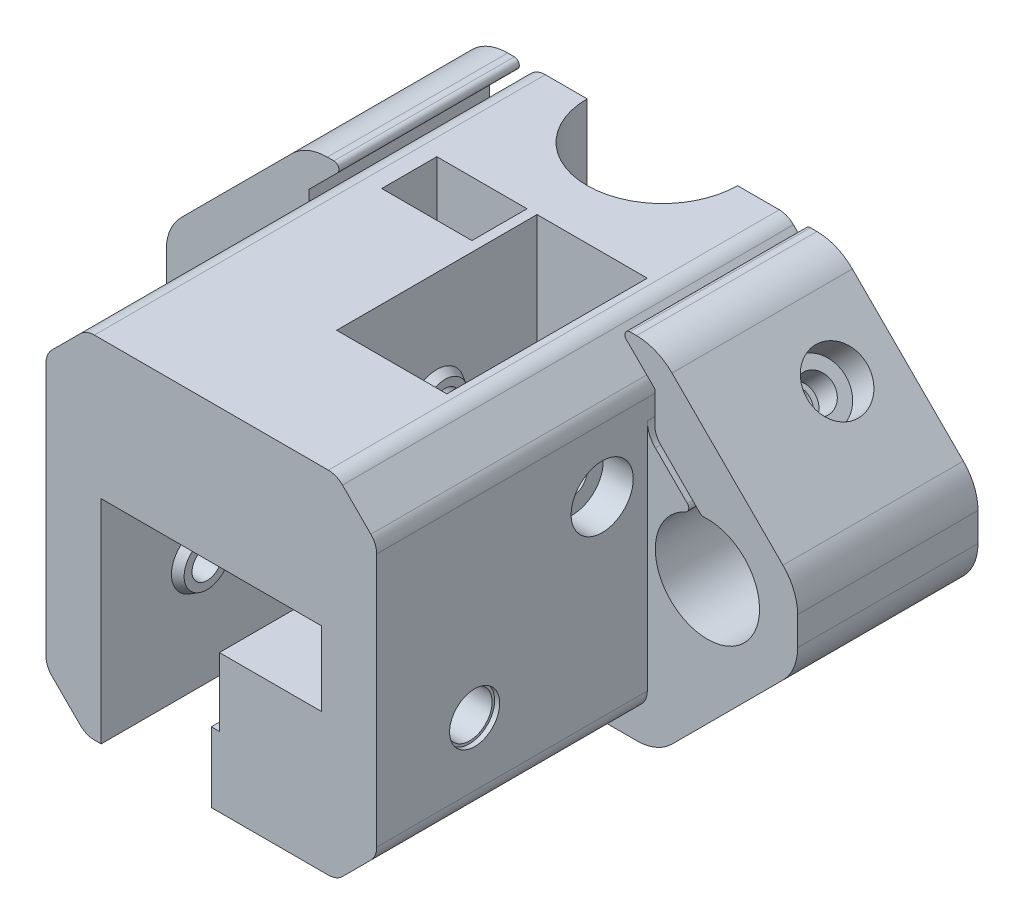
SolidWorks part; units mm, degrees
ref_plane "XY" through (0, 0, 0) normal (0, 0, 1) x (1, 0, 0)
ref_plane "XZ" through (0, 0, 0) normal (0, 1, 0) x (1, 0, 0)
ref_plane "YZ" through (0, 0, 0) normal (1, 0, 0) x (0, 0, -1)
sketch "Sketch1" plane through (0, 0, 0) normal (0, 0, 1) x (1, 0, 0)
  line L0 (-17.5, 17.5) -> (-31.5, 3.5)
  line L1 (31.5, -17.5) -> (17.5, -17.5) construction
  line L2 (31.5, -17.5) -> (31.5, -3.5) construction
  line L3 (31.5, 17.5) -> (17.5, 17.5) construction
  line L4 (-31.5, -17.5) -> (-31.5, -3.5) construction
  line L5 (31.5, -17.5) -> (-31.5, 17.5) construction
  line L6 (31.5, 17.5) -> (-31.5, -17.5) construction
  line L7 (-12.5, 17.5) -> (-16.5, 13.5)
  line L8 (-16.5, 13.5) -> (-16.5, 9.535)
  line L9 (-16.5, 9.535) -> (-21.0432, 4.9918)
  line L10 (-13.5607, 17.5) -> (-17.25, 13.8107)
  line L11 (-17.25, 13.8107) -> (-17.25, 9.8457)
  line L12 (-17.25, 9.8457) -> (-21.9273, 5.1684)
  line L13 (-17.25, 9.8457) -> (-21.5736, 5.5221) construction
  line L14 (-13.0303, 18.0303) -> (-17.25, 13.8107) construction
  line L15 (-13.5607, 17.5) -> (-17.5, 17.5)
  line L16 (0, 0) -> (-59.6161, 0) construction
  line L17 (0, 0) -> (0, 36.6742) construction
  line L18 (-17.5, -17.5) -> (-31.5, -3.5)
  line L19 (17.5, -17.5) -> (31.5, -3.5)
  line L20 (16.5, 9.535) -> (21.0432, 4.9918)
  line L21 (16.5, 13.5) -> (16.5, 9.535)
  line L22 (12.5, 17.5) -> (16.5, 13.5)
  line L23 (13.5607, 17.5) -> (17.25, 13.8107)
  line L24 (17.25, 13.8107) -> (17.25, 9.8457)
  line L25 (17.25, 9.8457) -> (21.9273, 5.1684)
  line L26 (17.5, 17.5) -> (31.5, 3.5)
  line L27 (12.5, 17.5) -> (-12.5, 17.5)
  line L28 (-17.5, 17.5) -> (-31.5, 17.5) construction
  line L29 (-31.5, 3.5) -> (-31.5, 17.5) construction
  line L30 (-31.5, -3.5) -> (-31.5, 3.5)
  line L31 (-17.5, -17.5) -> (-31.5, -17.5) construction
  line L32 (17.5, -17.5) -> (-17.5, -17.5)
  line L33 (31.5, -3.5) -> (31.5, 3.5)
  line L34 (31.5, 3.5) -> (31.5, 17.5) construction
  line L35 (17.5, 17.5) -> (13.5607, 17.5)
  arc A0 (-21.9273, 5.1684) -> (-21.0432, 4.9918) centre (-22.5, 0) ccw
  arc A1 (21.9273, 5.1684) -> (21.0432, 4.9918) centre (22.5, 0) cw
  point P0 (0, 0)
  dimension "D1" = 63
  dimension "D6" = 10.4
  dimension "D2" = 35
  dimension "D3" = 14
  dimension "D4" = 14
  dimension "D5" = 22.5
  dimension "D7" = 19
  dimension "D8" = 15
  dimension "D9" = 9.535
  dimension "D10" = 0.75
extrude "Boss-Extrude1" add sketch "Sketch1" along normal blind 18
sketch "Sketch2" plane through (0, 17.5, 0) normal (0, 1, 0) x (1, 0, 0)
  line L0 (12.5, 0) -> (-12.5, 0) construction
  line L1 (12.5, -18) -> (-12.5, -18) construction
  line L2 (-10, -18) -> (-1, -18)
  line L3 (-10, -18) -> (-10, -12.5)
  line L4 (-10, -12.5) -> (-1, -12.5)
  line L5 (-1, -18) -> (-1, -12.5)
  circle A0 centre (0, 0) radius 7.5
  point P10 (-5.5, -12.5)
  dimension "D1" = 15
  dimension "D2" = 9
  dimension "D3" = 5.5
  dimension "D4" = 5.5
extrude "Cut-Extrude1" cut sketch "Sketch2" against normal through all
fillet "Fillet1" radius 5 8 edges at (17.5, 17.5, 9) (31.5, 3.5, 9) (31.5, -3.5, 9) (17.5, -17.5, 9) (-17.5, -17.5, 9) (-31.5, -3.5, 9) (-31.5, 3.5, 9) (-17.5, 17.5, 9)
fillet "Fillet2" radius 0.5 6 edges at (-21.9273, 5.1684, 9) (-21.0432, 4.9918, 9) (21.0432, 4.9918, 9) (21.9273, 5.1684, 9) (-13.5607, 17.5, 9) (13.5607, 17.5, 9)
fillet "Fillet3" radius 2 2 edges at (17.25, 9.8457, 9) (-17.25, 9.8457, 9)
fillet "Fillet4" radius 2.75 2 edges at (-16.5, 9.535, 9) (16.5, 9.535, 9)
sketch "Sketch3" plane through (-17.5, 17.5, 0) normal (-0.7071, 0.7071, 0) x (0, 0, 1)
  line L0 (0, -2.0711) -> (0, -17.7279) construction
  circle A0 centre (6, -8.4) radius 1.75
  point P6 (-12.8431, 2.7076)
  dimension "D1" = 3.5
  dimension "D2" = 6
  dimension "D3" = 8.4
ref_plane "Plane1" through (0, 0, 6) normal (0, 0, -1) x (-1, 0, 0)
sketch "Sketch4" plane through (0, 0, 6) normal (0, 0, -1) x (-1, 0, 0)
  line L0 (23.4397, 11.5603) -> (11.3618, -0.5176) construction
  line L1 (24.6771, 10.3229) -> (22.2023, 12.7977) construction
  line L2 (23.4397, 11.5603) -> (25.561, 9.439)
  line L3 (18.9645, 16.0355) -> (30.0355, 4.9645) construction
  line L4 (25.561, 9.439) -> (23.4397, 7.3177)
  line L5 (23.4397, 7.3177) -> (22.5558, 8.2015)
  line L6 (12.8331, 0.9537) -> (23.4397, 11.5603)
  line L9 (22.5558, 8.2015) -> (14.0705, -0.2837)
  line L10 (14.0705, -0.2837) -> (12.8331, 0.9537)
  dimension "D1" = 3
  dimension "D2" = 1.75
  dimension "D3" = 3
  dimension "D4" = 15
revolve "Cut-Revolve1" cut sketch "Sketch4" angle 360 about L0
sketch "Sketch6" plane through (-6.8934, 6.8934, 0) normal (-0.7071, 0.7071, 0) x (0, 0, 1)
  line L0 (0, -2.0711) -> (0, -17.7279) construction
  line L1 (3.425, -9.8867) -> (6, -11.3734)
  line L2 (6, -11.3734) -> (8.575, -9.8867)
  line L3 (8.575, -9.8867) -> (8.575, -6.9133)
  line L4 (8.575, -6.9133) -> (6, -5.4266)
  line L5 (6, -5.4266) -> (3.425, -6.9133)
  line L6 (3.425, -6.9133) -> (3.425, -9.8867)
  circle A0 centre (6, -8.4) radius 2.575 construction
  dimension "D1" = 5.15
extrude "Cut-Extrude2" cut sketch "Sketch6" against normal blind 15
mirror "Mirror1" about plane through (0, 0, 0) normal (1, 0, 0) of "Cut-Extrude2", "Cut-Revolve1"
sketch "Sketch7" plane through (0, 0, 0) normal (0, 0, -1) x (-1, 0, 0)
  circle A0 centre (-12.5, 12.5) radius 1.6
  dimension "D1" = 3.2
  dimension "D2" = 12.5
  dimension "D3" = 12.5
extrude "Cut-Extrude3" cut sketch "Sketch7" against normal blind 10
sketch "Sketch8" plane through (0, 0, 0) normal (0, 0, -1) x (-1, 0, 0)
  circle A0 centre (-12.5, 12.5) radius 2.35
  dimension "D1" = 4.7
extrude "Cut-Extrude4" cut sketch "Sketch8" against normal blind 5
sketch "Sketch9" plane through (0, 0, 0) normal (0, 0, -1) x (-1, 0, 0)
  circle A0 centre (-12.5, 12.5) radius 2.5
  dimension "D1" = 5
extrude "Cut-Extrude5" cut sketch "Sketch9" against normal blind 0.5
mirror "Mirror2" about plane through (0, 0, 0) normal (0, 1, 0) of "Cut-Extrude5", "Cut-Extrude4", "Cut-Extrude3"
mirror "Mirror3" about plane through (0, 0, 0) normal (1, 0, 0) of "Mirror2", "Cut-Extrude5", "Cut-Extrude4", "Cut-Extrude3"
sketch "Sketch10" plane through (0, 0, 18) normal (0, 0, 1) x (1, 0, 0)
  line L0 (12.5, 17.5) -> (-1, 17.5) construction
  line L1 (16.5, 13.5) -> (12.5, 17.5) construction
  line L2 (16.5, 10.6741) -> (16.5, 13.5) construction
  line L3 (12.5, 17.5) -> (-12.5, 17.5)
  line L4 (16.5, 13.5) -> (12.5, 17.5)
  line L5 (16.5, -13.5) -> (16.5, 13.5)
  line L6 (0, -17.5) -> (0, 17.5) construction
  line L7 (0, 0) -> (16.5, 0) construction
  line L8 (-16.5, -13.5) -> (-16.5, 13.5)
  line L9 (-16.5, 13.5) -> (-12.5, 17.5)
  line L10 (-16.5, -13.5) -> (-12.5, -17.5)
  line L11 (16.5, -13.5) -> (12.5, -17.5)
  line L12 (12.5, -17.5) -> (-12.5, -17.5)
  point P14 (-16.5, 0)
extrude "Boss-Extrude2" add sketch "Sketch10" along normal offset from surface (27 mm away) 45 up to face at (-10, -12.5, 0)
sketch "Sketch11" plane through (0, 17.5, 0) normal (0, 1, 0) x (1, 0, 0)
  line L0 (-1, -12.5) -> (-10, -12.5) construction
  line L1 (0, -12.5) -> (11, -12.5)
  line L2 (0, -12.5) -> (0, -32.5)
  line L3 (0, -32.5) -> (11, -32.5)
  line L4 (11, -12.5) -> (11, -32.5)
  dimension "D1" = 20
  dimension "D2" = 11
extrude "Cut-Extrude6" cut sketch "Sketch11" against normal blind 21.2
sketch "Sketch12" plane through (0, 0, 32.5) normal (0, 0, -1) x (-1, 0, 0)
  line L0 (0, -3.7) -> (-11, -3.7) construction
  line L1 (0, -3.7) -> (-11, -3.7)
  line L2 (0, 0) -> (-16.491, 0) construction
  line L3 (-11, -3.7) -> (-11, 3.7)
  line L4 (-11, 3.7) -> (0, 3.7)
  line L5 (0, 3.7) -> (0, -3.7)
  line L6 (0, -3.7) -> (0, -3.5912)
  line M2 (-11, 17.5) -> (-11, -3.7)
  line M3 (-11, -3.7) -> (0, -3.7)
  line M4 (0, -3.7) -> (0, 17.5)
extrude "Cut-Extrude7" cut sketch "Sketch12" against normal up to surface (12.5 mm away) contours L2 L4 M4 M2 | L5 L2 L3 M3 M4 region at (5.5, -1.85, 32.5) region at (5.5, 1.85, 32.5) up to face at (0, 0, 45)
fillet "Fillet5" radius 10 1 edges at (5.5, -3.7, 12.5)
sketch "Sketch13" plane through (0, -17.5, 0) normal (0, -1, 0) x (1, 0, 0)
  line L1 (0, 45) -> (-11, 45)
  line L2 (0, 45) -> (0, 25.2)
  line L3 (0, 25.2) -> (-11, 25.2)
  line L4 (-11, 45) -> (-11, 25.2)
  dimension "D1" = 11
  dimension "D2" = 19.8
extrude "Cut-Extrude8" cut sketch "Sketch13" against normal up to surface (21.2 mm away) up to face at (5.5, 3.7, 38.75)
fillet "Fillet6" radius 10 1 edges at (-5.5, 3.7, 25.2) tangent propagation no
sketch "Sketch14" plane through (0, 0, 45) normal (0, 0, 1) x (1, 0, 0)
  line L0 (-11, 3.7) -> (11, 3.7) construction
  line L1 (11, -3.7) -> (11, 3.7) construction
  line L2 (0, -3.7) -> (11, -3.7) construction
  line L3 (0, 3.7) -> (11, 3.7)
  line L4 (11, -3.7) -> (11, 3.7)
  line L5 (0, -3.7) -> (11, -3.7)
  line L6 (0, -3.7) -> (0, 3.7)
extrude "Cut-Extrude9" cut sketch "Sketch14" against normal up to surface (12.5 mm away) up to face at (5.5, 10.4143, 32.5)
sketch "Sketch15" plane through (-11, 0, 0) normal (1, 0, 0) x (0, 0, -1)
  circle A0 centre (-35.23, -6.365) radius 2.75
  dimension "D1" = 5.5
  dimension "D2" = 35.23
  dimension "D3" = 6.365
extrude "Boss-Extrude3" add sketch "Sketch15" along normal blind 0.8 draft 30
sketch "Sketch16" plane through (0, 0, 0) normal (-1, 0, 0) x (0, 0, 1)
  line L1 (45, -3.7) -> (31, -3.7)
  line L2 (45, -3.7) -> (45, -10.515)
  line L3 (45, -10.515) -> (31, -10.515)
  line L4 (31, -3.7) -> (31, -10.515)
  dimension "D1" = 6.815
  dimension "D2" = 14
extrude "Cut-Extrude10" cut sketch "Sketch16" against normal blind 0.8
ref_plane "Plane2" through (0, 0, 35.23) normal (0, 0, 1) x (1, 0, 0)
sketch "Sketch17" plane through (0, 0, 35.23) normal (0, 0, 1) x (1, 0, 0)
  line L0 (31.9477, -6.365) -> (-32.235, -6.365) construction
  line L2 (-11, -9.115) -> (-11, -3.615) construction
  line L3 (-11, -9.115) -> (-11, -3.615) construction
  line L4 (-16.5, -6.365) -> (-16.5, -3.265)
  line L5 (-16.5, 10.6741) -> (-16.5, -13.5) construction
  line L6 (-16.5, -3.265) -> (-13.5, -3.265)
  line L7 (-13.5, -3.265) -> (-13.5, -4.865)
  line L8 (-13.5, -4.865) -> (11.5, -4.865)
  line L9 (11.5, -4.865) -> (11.5, -4.115)
  line L10 (11.5, -4.115) -> (16, -4.115)
  line L11 (16, -4.115) -> (16, -3.865)
  line L12 (16, -3.865) -> (16.5, -3.865)
  line L13 (16.5, 13.5) -> (16.5, -13.5) construction
  line L14 (16.5, -3.865) -> (16.5, -6.365)
  line L15 (16.5, -13.5) -> (16.5, 10.6741) construction
  line L16 (16.5, -6.365) -> (-16.5, -6.365)
  point P5 (-11, -6.365)
  dimension "D1" = 3
  dimension "D2" = 3.1
  dimension "D3" = 1.5
  dimension "D4" = 2.25
  dimension "D5" = 2.5
  dimension "D6" = 0.5
  dimension "D7" = 5
revolve "Cut-Revolve2" cut sketch "Sketch17" angle 360 about L0
sketch "Sketch18" plane through (11, 0, 0) normal (-1, 0, 0) x (0, 0, 1)
  circle A0 centre (22.5, 6.365) radius 1.5
  dimension "D1" = 6.365
  dimension "D3" = 3
  dimension "D2" = 22.5
sketch "Sketch19" plane through (11, 0, 0) normal (-1, 0, 0) x (0, 0, 1)
  circle A0 centre (22.5, 6.365) radius 2.75
  dimension "D1" = 5.5
extrude "Boss-Extrude4" add sketch "Sketch19" along normal blind 0.8 draft 30
ref_plane "Plane3" through (5.5, 0, 0) normal (1, 0, 0) x (0, 0, -1)
mirror "Mirror4" about plane through (5.5, 0, 0) normal (1, 0, 0) of "Boss-Extrude4"
ref_plane "Plane4" through (0, 0, 22.5) normal (0, 0, 1) x (1, 0, 0)
sketch "Sketch20" plane through (0, 0, 22.5) normal (0, 0, 1) x (1, 0, 0)
  line L0 (11, 6.365) -> (-21.7769, 6.365) construction
  line L1 (16.5, 6.365) -> (16.5, 9.465)
  line L2 (16.5, 13.5) -> (16.5, -13.5) construction
  line L3 (16.5, 9.465) -> (13.5, 9.465)
  line L4 (13.5, 9.465) -> (13.5, 7.865)
  line L5 (13.5, 7.865) -> (-11.5, 7.865)
  line L6 (-11.5, 7.865) -> (-11.5, 8.615)
  line L7 (-11.5, 8.615) -> (-16, 8.615)
  line L8 (-16, 8.615) -> (-16, 8.865)
  line L9 (-16, 8.865) -> (-16.5, 8.865)
  line L10 (-16.5, -13.5) -> (-16.5, 13.5) construction
  line L11 (-16.5, 8.865) -> (-16.5, 6.365)
  line L12 (-16.5, 10.6741) -> (-16.5, -13.5) construction
  line L13 (-16.5, 6.365) -> (16.5, 6.365)
  dimension "D1" = 3.1
  dimension "D2" = 3
  dimension "D3" = 1.5
  dimension "D4" = 2.25
  dimension "D5" = 2.5
  dimension "D6" = 0.5
  dimension "D7" = 25
revolve "Cut-Revolve3" cut sketch "Sketch20" angle 360 about L0
fillet "Fillet7" radius 2 8 edges at (16.5, -13.5, 31.5) (12.5, -17.5, 31.5) (-12.5, -17.5, 31.5) (-16.5, -13.5, 31.5) (16.5, 13.5, 22.5) (12.5, 17.5, 22.5) (-12.5, 17.5, 22.5) (-16.5, 13.5, 22.5)
